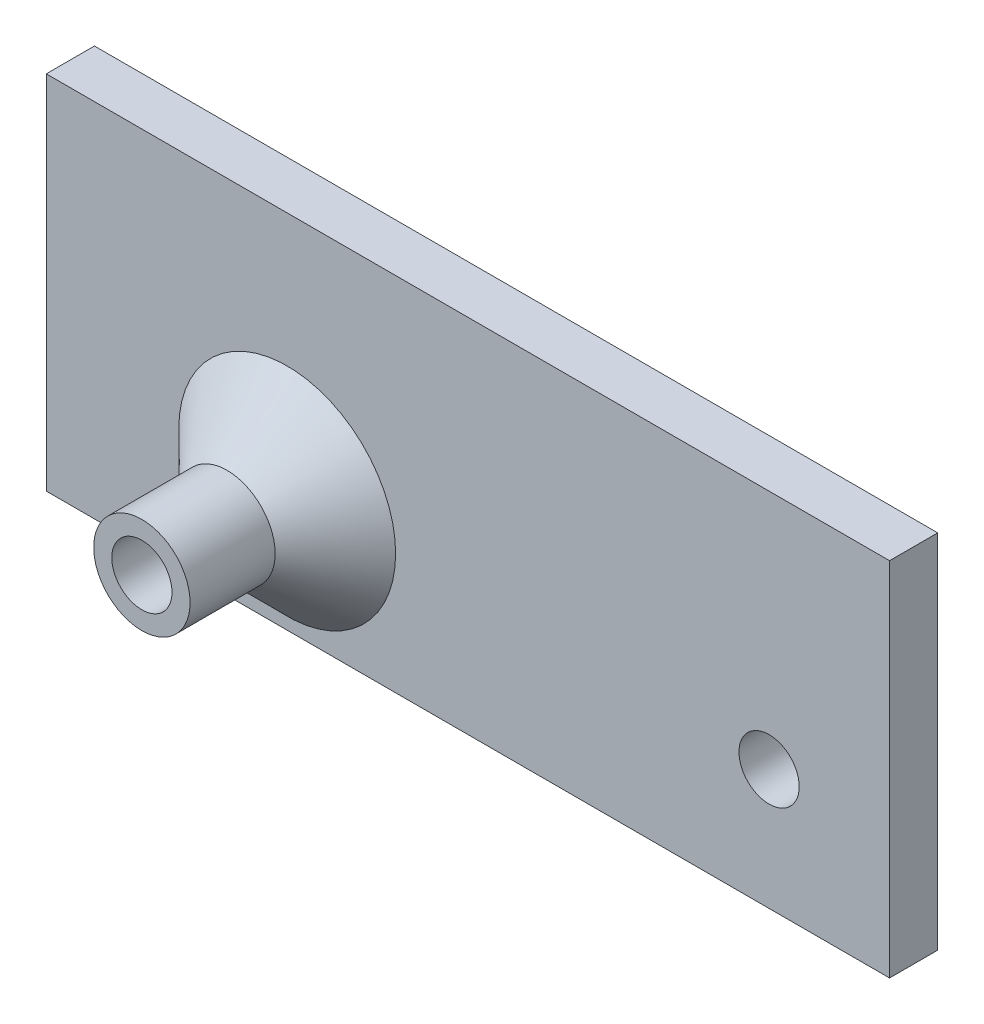
SolidWorks part; units mm, degrees
ref_plane "Front Plane" through (0, 0, 0) normal (0, 0, 1) x (1, 0, 0)
ref_plane "Top Plane" through (0, 0, 0) normal (0, 1, 0) x (1, 0, 0)
ref_plane "Right Plane" through (0, 0, 0) normal (1, 0, 0) x (0, 0, -1)
sketch "Sketch1" plane through (0, 0, 0) normal (0, 0, 1) x (1, 0, 0)
  line L5 (-20, 20) -> (50, 20)
  line L6 (-20, 20) -> (-20, -10)
  line L7 (-20, -10) -> (50, -10)
  line L8 (50, 20) -> (50, -10)
  circle A0 centre (0, 0) radius 2.5
  circle A1 centre (40, 0) radius 2.5
  circle A2 centre (0, 0) radius 4
  circle A3 centre (40, 0) radius 4
  point P0 (0, 0)
  dimension "D3" = 5
  dimension "D7" = 8
  dimension "D1" = 30
  dimension "D2" = 20
  dimension "D4" = 70
  dimension "D5" = 10
  dimension "D6" = 10
extrude "Boss-Extrude1" add sketch "Sketch1" along normal blind 4 contours L8 L5 L6 L7 A3 A2 | A3 A1 region at (14.7486, 5.2514, 0) region at (36.1131, 0, 0)
extrude "Boss-Extrude2" add sketch "Sketch1<3>" along normal blind 16.063 contours A2 A0 region at (-3.8869, 0, 0)
sketch "Sketch1<3>" plane through (0, 0, 0) normal (0, 0, 1) x (1, 0, 0) same geometry as "Sketch1"
chamfer "Chamfer1" distance 5 angle 45 1 edges at (4, 0, 4)
